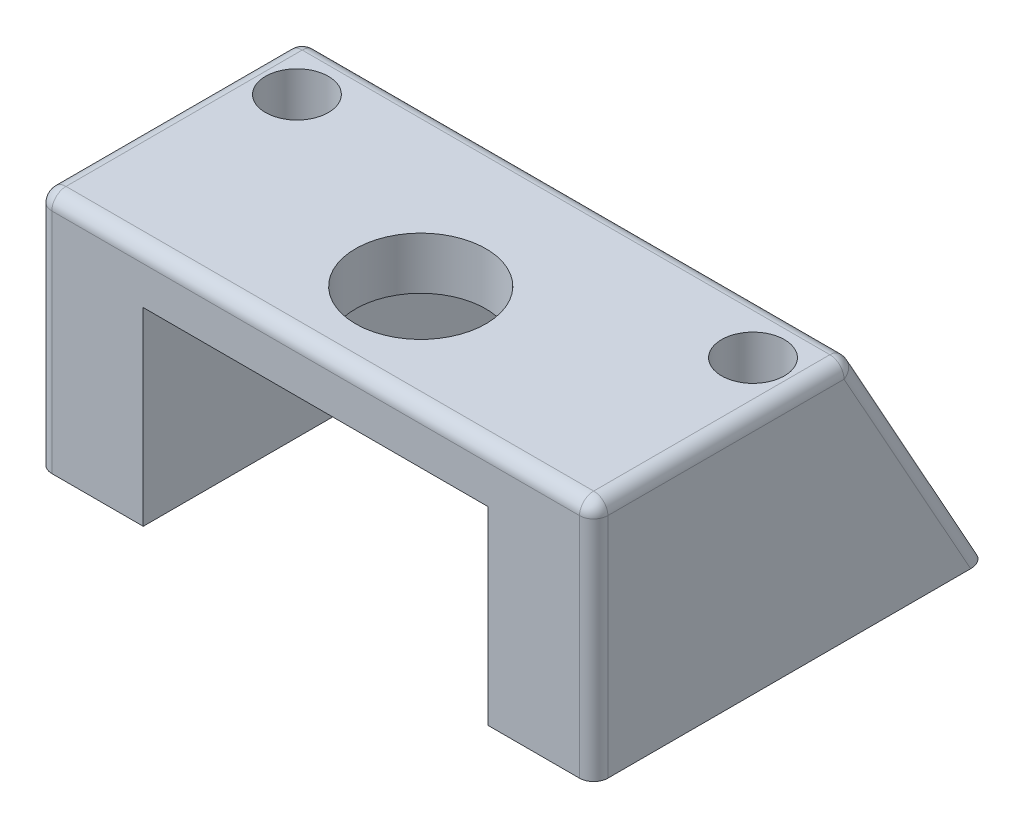
SolidWorks part; units mm, degrees
ref_plane "Front Plane" through (0, 0, 0) normal (0, 0, 1) x (1, 0, 0)
ref_plane "Top Plane" through (0, 0, 0) normal (0, 1, 0) x (1, 0, 0)
ref_plane "Right Plane" through (0, 0, 0) normal (1, 0, 0) x (0, 0, -1)
sketch "Sketch1" plane through (0, 0, 0) normal (1, 0, 0) x (0, 0, -1)
  line L0 (15.0876, -9.271) -> (4.7655, 9.271)
  line L1 (-15.0876, -9.271) -> (15.0876, -9.271)
  line L2 (-15.0876, -9.271) -> (-15.0876, 9.271)
  line L3 (-15.0876, 9.271) -> (15.0876, 9.271)
  line L4 (15.0876, -9.271) -> (15.0876, 9.271)
  line L5 (-15.0876, -9.271) -> (15.0876, 9.271) construction
  line L6 (-15.0876, 9.271) -> (15.0876, -9.271) construction
  line L7 (-15.0876, -9.271) -> (7.9487, 3.553) construction
  line L8 (-15.0876, 9.271) -> (-15.0876, 11.176) construction
  line L9 (-15.0876, 11.176) -> (4.7655, 11.176) construction
  line L10 (4.7655, 11.176) -> (4.7655, 9.271) construction
  line L12 (-14.0002, 13.081) -> (3.6782, 13.081) construction
  line L13 (-14.0002, 13.081) -> (-14.0002, 9.271) construction
  line L14 (-14.0002, 9.271) -> (3.6782, 9.271) construction
  line L15 (3.6782, 13.081) -> (3.6782, 9.271) construction
  line L16 (-14.0002, 13.081) -> (3.6782, 9.271) construction
  line L17 (-14.0002, 9.271) -> (3.6782, 13.081) construction
  arc A0 (-14.0002, 9.271) -> (-15.0876, 8.1836) centre (-14.0002, 8.1836) ccw
  arc A1 (3.6782, 9.271) -> (5.2944, 8.3209) centre (3.6782, 7.4212) cw
  point P0 (0, 0)
  point P10 (-5.161, 11.176)
  dimension "D1" = 18.542
  dimension "D2" = 30.1752
  dimension "D3" = 26.3652
  dimension "D4" = 1.905
  dimension "D5" = 17.6784
extrude "Boss-Extrude1" add sketch "Sketch1" along normal mid plane 42.672 contours L3 L2 L1 L0 | A0 L3 L2 | L3 A1 L0 region at (0, -0.6469, 2.3992) region at (0, 9.0714, -4.6482) region at (0, 9.0281, 14.8447)
sketch "Sketch2" plane through (0, 0, 0) normal (0, 0, 1) x (1, 0, 0)
  line L0 (21.336, -9.271) -> (-21.336, -9.271) construction
  line L1 (-13.2334, 5.271) -> (13.2334, 5.271)
  line L2 (-13.2334, 5.271) -> (-13.2334, -9.271)
  line L3 (-13.2334, -9.271) -> (13.2334, -9.271)
  line L4 (13.2334, 5.271) -> (13.2334, -9.271)
  line L5 (-13.2334, 5.271) -> (13.2334, -9.271) construction
  line L6 (-13.2334, -9.271) -> (13.2334, 5.271) construction
  line L8 (21.336, 9.271) -> (-21.336, 9.271) construction
  line L9 (21.336, -9.271) -> (21.336, 9.271) construction
  point P0 (0, -2)
  dimension "D1" = 8.1026
  dimension "D2" = 4
extrude "Cut-Extrude1" cut sketch "Sketch2" against normal through all both and the other way through all
sketch "Sketch3" plane through (0, 0, 0) normal (0, 1, 0) x (1, 0, 0)
  line L0 (21.336, -15.0876) -> (-21.336, -15.0876) construction
  line L8 (21.336, -15.0876) -> (21.336, 4.7655) construction
  line L9 (21.336, -1.4338) -> (21.336, -15.0876) construction
  circle A2 centre (0, -7.025) radius 2.5 construction
  circle A3 centre (0, -7.025) radius 5
  dimension "D1" = 5.5626
  dimension "D2" = 5
  dimension "D5" = 10
fillet "Fillet1" radius 1.0874 8 edges at (0, 9.271, -4.7655) (21.336, 9.271, 5.161) (0, 9.271, 15.0876) (-21.336, 9.271, 5.161) (-21.336, 0, -9.9266) (-21.336, 0, 15.0876) (21.336, 0, 15.0876) (21.336, 0, -9.9266)
extrude "Cut-Extrude2" cut sketch "Sketch3" against normal through all both and the other way through all
sketch "StepperAlignmentSketch" plane through (0, 0, 0) normal (0, 1, 0) x (1, 0, 0)
  line L0 (0, -7.025) -> (17.5, -15.025) construction
  line L1 (17.5, -15.025) -> (-17.5, -15.025) construction
  line L2 (-17.5, -15.025) -> (0, -7.025) construction
  line L3 (0, -7.025) -> (13.2334, -7.025) construction
  line L4 (13.2334, 6.9923) -> (13.2334, -15.0876) construction
  line L5 (17.5, 0.975) -> (-17.5, 0.975) construction
  line L6 (-17.5, 0.975) -> (0, -7.025) construction
  line L7 (0, -7.025) -> (17.5, 0.975) construction
  point P9 (0, -15.025)
  dimension "D1" = 19.2419
  dimension "D2" = 35
sketch "Sketch4" plane through (0, 0, 0) normal (0, 1, 0) x (1, 0, 0)
  line L0 (-21.336, -14.0002) -> (-13.2334, -14.0002)
  line L1 (-13.2334, 6.9923) -> (-13.2334, -15.0876) construction
  line L2 (-13.2334, -15.0876) -> (-20.2486, -15.0876) construction
  line L3 (-17.2847, -14.0002) -> (-17.2847, -15.0876) construction
  line L40 (-14.3208, -14.0002) -> (-14.3208, 14.0002)
  line L41 (-14.3208, 14.0002) -> (-20.2486, 14.0002)
  line L42 (-20.2486, 14.0002) -> (-20.2486, -14.0002)
  line L43 (-20.2486, 0) -> (-21.336, 0) construction
  line L44 (-17.9322, -1.4761) -> (-17.5, -1.5523) construction
  line L45 (-17.5, -1.2947) -> (-16.7237, -1.1578) construction
  line L46 (-16.7237, -1.1578) -> (-16.0411, -0.7637) construction
  line L47 (-17.2847, 14.0002) -> (-17.2847, 15.0876) construction
  line L48 (-13.2334, 15.0876) -> (-20.2486, 15.0876) construction
  line L49 (-16.0411, -0.7637) -> (-15.5344, -0.1598) construction
  line L50 (-14.3208, 0) -> (-13.2334, 0) construction
  line L51 (-21.336, -14.0002) -> (-21.336, 13.8431) construction
  line L52 (-15.5344, -0.1598) -> (-15.2648, 0.5809) construction
  line L53 (-15.2648, 0.5809) -> (-15.2648, 1.3691) construction
  line L54 (-15.2648, 1.3691) -> (-15.5344, 2.1098) construction
  line L55 (-15.5344, 2.1098) -> (-16.0411, 2.7137) construction
  line L56 (-21.336, -14.0002) -> (-21.336, 4.1263) construction
  line L57 (-21.336, -14.0002) -> (-21.336, 4.1263)
  line L58 (-16.0411, 2.7137) -> (-16.7237, 3.1078) construction
  line L59 (-16.7237, 3.1078) -> (-17.5, 3.2447) construction
  line L60 (-17.5, 3.2447) -> (-18.2763, 3.1078) construction
  line L61 (-18.2763, 3.1078) -> (-18.9589, 2.7137) construction
  line L62 (-18.9589, 2.7137) -> (-19.4656, 2.1098) construction
  line L63 (-19.4656, 2.1098) -> (-19.7352, 1.3691) construction
  line L64 (-19.7352, 1.3691) -> (-19.7352, 0.5809) construction
  line L65 (-19.7352, 0.5809) -> (-19.4656, -0.1598) construction
  line L66 (-19.4656, -0.1598) -> (-18.9589, -0.7637) construction
  line L67 (-18.9589, -0.7637) -> (-18.2763, -1.1578) construction
  line L68 (-18.2763, -1.1578) -> (-17.5, -1.2947) construction
  line L69 (-15.0111, 0.975) -> (-15.1612, 1.8263) construction
  line L70 (-15.1612, 1.8263) -> (-15.5934, 2.5748) construction
  line L71 (-15.5934, 2.5748) -> (-16.2555, 3.1305) construction
  line L72 (-16.2555, 3.1305) -> (-17.0678, 3.4261) construction
  line L73 (-17.0678, 3.4261) -> (-17.9322, 3.4261) construction
  line L74 (-17.9322, 3.4261) -> (-18.7445, 3.1305) construction
  line L75 (-18.7445, 3.1305) -> (-19.4066, 2.5748) construction
  line L76 (-19.4066, 2.5748) -> (-19.8388, 1.8263) construction
  line L77 (-19.8388, 1.8263) -> (-19.9889, 0.975) construction
  line L78 (-19.9889, 0.975) -> (-19.8388, 0.1237) construction
  line L79 (-19.8388, 0.1237) -> (-19.4066, -0.6248) construction
  line L80 (-19.4066, -0.6248) -> (-18.7445, -1.1805) construction
  line L81 (-18.7445, -1.1805) -> (-17.9322, -1.4761) construction
  line L82 (-17.9322, -1.4761) -> (-17.0678, -1.4761) construction
  line L83 (-17.0678, -1.4761) -> (-16.2555, -1.1805) construction
  line L84 (-16.2555, -1.1805) -> (-15.5934, -0.6248) construction
  line L85 (-15.5934, -0.6248) -> (-15.1612, 0.1237) construction
  line L86 (-15.1612, 0.1237) -> (-15.0111, 0.975) construction
  line L87 (-17.5, -1.5523) -> (-17.0678, -1.4761) construction
  line L89 (-17.5, -1.2947) -> (-16.5746, -1.2947) construction
  line L90 (-17.9322, -1.4761) -> (-17.7121, -1.3948) construction
  line L91 (-17.7121, -1.3948) -> (-17.5, -1.2947) construction
  line L92 (-17.5, -1.2947) -> (-17.2879, -1.3948) construction
  line L93 (-17.2879, -1.3948) -> (-17.0678, -1.4761) construction
  circle A1 centre (-17.5, 0.975) radius 2.2352 construction
  circle A2 centre (-17.5, 0.975) radius 2.4511 construction
  circle A75 centre (-17.5, 0.975) radius 3.9624
  arc A76 (-17.9322, -1.4761) -> (-17.7121, -1.3948) centre (-17.8918, -1.2469) ccw
  arc A77 (-17.7121, -1.3948) -> (-17.5, -1.2947) centre (-17.5, -1.5694) cw
  arc A78 (-17.5, -1.2947) -> (-17.2879, -1.3948) centre (-17.5, -1.5694) cw
  arc A79 (-17.2879, -1.3948) -> (-17.0678, -1.4761) centre (-17.1082, -1.2469) ccw
  arc A80 (-18.1112, -1.3245) -> (-17.9322, -1.4761) centre (-17.8918, -1.2469) ccw
  arc A81 (-18.2763, -1.1578) -> (-18.1112, -1.3245) centre (-18.3702, -1.416) cw
  arc A82 (-18.5099, -1.1794) -> (-18.2763, -1.1578) centre (-18.3702, -1.416) cw
  arc A83 (-18.7445, -1.1805) -> (-18.5099, -1.1794) centre (-18.6281, -0.9789) ccw
  circle A84 centre (-17.5, 0.975) radius 2.2352 construction
  arc A85 (-18.8608, -0.9768) -> (-18.7445, -1.1805) centre (-18.6281, -0.9789) ccw
  arc A86 (-18.9589, -0.7637) -> (-18.8608, -0.9768) centre (-19.1355, -0.9742) cw
  arc A87 (-19.1858, -0.704) -> (-18.9589, -0.7637) centre (-19.1355, -0.9742) cw
  arc A88 (-19.4066, -0.6248) -> (-19.1858, -0.704) centre (-19.2284, -0.4753) ccw
  circle A89 centre (-17.5, 0.975) radius 2.2352 construction
  arc A90 (-19.4463, -0.3936) -> (-19.4066, -0.6248) centre (-19.2284, -0.4753) ccw
  arc A91 (-19.4656, -0.1598) -> (-19.4463, -0.3936) centre (-19.7035, -0.2972) cw
  arc A92 (-19.6584, -0.0262) -> (-19.4656, -0.1598) centre (-19.7035, -0.2972) cw
  arc A93 (-19.8388, 0.1237) -> (-19.6584, -0.0262) centre (-19.6202, 0.2033) ccw
  circle A94 centre (-17.5, 0.975) radius 2.2352 construction
  arc A95 (-19.797, 0.3546) -> (-19.8388, 0.1237) centre (-19.6202, 0.2033) ccw
  arc A96 (-19.7352, 0.5809) -> (-19.797, 0.3546) centre (-20.0058, 0.5332) cw
  arc A97 (-19.8707, 0.7724) -> (-19.7352, 0.5809) centre (-20.0058, 0.5332) cw
  arc A98 (-19.9889, 0.975) -> (-19.8707, 0.7724) centre (-19.7562, 0.975) ccw
  circle A99 centre (-17.5, 0.975) radius 2.2352 construction
  arc A100 (-19.8707, 1.1776) -> (-19.9889, 0.975) centre (-19.7562, 0.975) ccw
  arc A101 (-19.7352, 1.3691) -> (-19.8707, 1.1776) centre (-20.0058, 1.4168) cw
  arc A102 (-19.797, 1.5954) -> (-19.7352, 1.3691) centre (-20.0058, 1.4168) cw
  arc A103 (-19.8388, 1.8263) -> (-19.797, 1.5954) centre (-19.6202, 1.7467) ccw
  circle A104 centre (-17.5, 0.975) radius 2.2352 construction
  arc A105 (-19.6584, 1.9762) -> (-19.8388, 1.8263) centre (-19.6202, 1.7467) ccw
  arc A106 (-19.4656, 2.1098) -> (-19.6584, 1.9762) centre (-19.7035, 2.2472) cw
  arc A107 (-19.4463, 2.3436) -> (-19.4656, 2.1098) centre (-19.7035, 2.2472) cw
  arc A108 (-19.4066, 2.5748) -> (-19.4463, 2.3436) centre (-19.2284, 2.4253) ccw
  circle A109 centre (-17.5, 0.975) radius 2.2352 construction
  arc A110 (-19.1858, 2.654) -> (-19.4066, 2.5748) centre (-19.2284, 2.4253) ccw
  arc A111 (-18.9589, 2.7137) -> (-19.1858, 2.654) centre (-19.1355, 2.9242) cw
  arc A112 (-18.8608, 2.9268) -> (-18.9589, 2.7137) centre (-19.1355, 2.9242) cw
  arc A113 (-18.7445, 3.1305) -> (-18.8608, 2.9268) centre (-18.6281, 2.9289) ccw
  circle A114 centre (-17.5, 0.975) radius 2.2352 construction
  arc A115 (-18.5099, 3.1294) -> (-18.7445, 3.1305) centre (-18.6281, 2.9289) ccw
  arc A116 (-18.2763, 3.1078) -> (-18.5099, 3.1294) centre (-18.3702, 3.366) cw
  arc A117 (-18.1112, 3.2745) -> (-18.2763, 3.1078) centre (-18.3702, 3.366) cw
  arc A118 (-17.9322, 3.4261) -> (-18.1112, 3.2745) centre (-17.8918, 3.1969) ccw
  circle A119 centre (-17.5, 0.975) radius 2.2352 construction
  arc A120 (-17.7121, 3.3448) -> (-17.9322, 3.4261) centre (-17.8918, 3.1969) ccw
  arc A121 (-17.5, 3.2447) -> (-17.7121, 3.3448) centre (-17.5, 3.5194) cw
  arc A122 (-17.2879, 3.3448) -> (-17.5, 3.2447) centre (-17.5, 3.5194) cw
  arc A123 (-17.0678, 3.4261) -> (-17.2879, 3.3448) centre (-17.1082, 3.1969) ccw
  circle A124 centre (-17.5, 0.975) radius 2.2352 construction
  arc A125 (-16.8888, 3.2745) -> (-17.0678, 3.4261) centre (-17.1082, 3.1969) ccw
  arc A126 (-16.7237, 3.1078) -> (-16.8888, 3.2745) centre (-16.6298, 3.366) cw
  arc A127 (-16.4901, 3.1294) -> (-16.7237, 3.1078) centre (-16.6298, 3.366) cw
  arc A128 (-16.2555, 3.1305) -> (-16.4901, 3.1294) centre (-16.3719, 2.9289) ccw
  circle A129 centre (-17.5, 0.975) radius 2.2352 construction
  arc A130 (-16.1392, 2.9268) -> (-16.2555, 3.1305) centre (-16.3719, 2.9289) ccw
  arc A131 (-16.0411, 2.7137) -> (-16.1392, 2.9268) centre (-15.8645, 2.9242) cw
  arc A132 (-15.8142, 2.654) -> (-16.0411, 2.7137) centre (-15.8645, 2.9242) cw
  arc A133 (-15.5934, 2.5748) -> (-15.8142, 2.654) centre (-15.7716, 2.4253) ccw
  circle A134 centre (-17.5, 0.975) radius 2.2352 construction
  arc A135 (-15.5537, 2.3436) -> (-15.5934, 2.5748) centre (-15.7716, 2.4253) ccw
  arc A136 (-15.5344, 2.1098) -> (-15.5537, 2.3436) centre (-15.2965, 2.2472) cw
  arc A137 (-15.3416, 1.9762) -> (-15.5344, 2.1098) centre (-15.2965, 2.2472) cw
  arc A138 (-15.1612, 1.8263) -> (-15.3416, 1.9762) centre (-15.3798, 1.7467) ccw
  circle A139 centre (-17.5, 0.975) radius 2.2352 construction
  arc A140 (-15.203, 1.5954) -> (-15.1612, 1.8263) centre (-15.3798, 1.7467) ccw
  arc A141 (-15.2648, 1.3691) -> (-15.203, 1.5954) centre (-14.9942, 1.4168) cw
  arc A142 (-15.1293, 1.1776) -> (-15.2648, 1.3691) centre (-14.9942, 1.4168) cw
  arc A143 (-15.0111, 0.975) -> (-15.1293, 1.1776) centre (-15.2438, 0.975) ccw
  circle A144 centre (-17.5, 0.975) radius 2.2352 construction
  arc A145 (-15.1293, 0.7724) -> (-15.0111, 0.975) centre (-15.2438, 0.975) ccw
  arc A146 (-15.2648, 0.5809) -> (-15.1293, 0.7724) centre (-14.9942, 0.5332) cw
  arc A147 (-15.203, 0.3546) -> (-15.2648, 0.5809) centre (-14.9942, 0.5332) cw
  arc A148 (-15.1612, 0.1237) -> (-15.203, 0.3546) centre (-15.3798, 0.2033) ccw
  circle A149 centre (-17.5, 0.975) radius 2.2352 construction
  arc A150 (-15.3416, -0.0262) -> (-15.1612, 0.1237) centre (-15.3798, 0.2033) ccw
  arc A151 (-15.5344, -0.1598) -> (-15.3416, -0.0262) centre (-15.2965, -0.2972) cw
  arc A152 (-15.5537, -0.3936) -> (-15.5344, -0.1598) centre (-15.2965, -0.2972) cw
  arc A153 (-15.5934, -0.6248) -> (-15.5537, -0.3936) centre (-15.7716, -0.4753) ccw
  circle A154 centre (-17.5, 0.975) radius 2.2352 construction
  arc A155 (-15.8142, -0.704) -> (-15.5934, -0.6248) centre (-15.7716, -0.4753) ccw
  arc A156 (-16.0411, -0.7637) -> (-15.8142, -0.704) centre (-15.8645, -0.9742) cw
  arc A157 (-16.1392, -0.9768) -> (-16.0411, -0.7637) centre (-15.8645, -0.9742) cw
  arc A158 (-16.2555, -1.1805) -> (-16.1392, -0.9768) centre (-16.3719, -0.9789) ccw
  circle A159 centre (-17.5, 0.975) radius 2.2352 construction
  arc A160 (-16.4901, -1.1794) -> (-16.2555, -1.1805) centre (-16.3719, -0.9789) ccw
  arc A161 (-16.7237, -1.1578) -> (-16.4901, -1.1794) centre (-16.6298, -1.416) cw
  arc A162 (-16.8888, -1.3245) -> (-16.7237, -1.1578) centre (-16.6298, -1.416) cw
  arc A163 (-17.0678, -1.4761) -> (-16.8888, -1.3245) centre (-17.1082, -1.2469) ccw
  circle A164 centre (-17.5, 0.975) radius 2.2352 construction
  point P246 (-17.5, 0.975)
  dimension "D1" = 4.4704
  dimension "D2" = 4.9022
  dimension "D3" = 7.9248
  dimension "D4" = 18
  dimension "D5" = 0.2748
  dimension "D6" = 0.2327
extrude "Cut-Extrude3" cut sketch "Sketch4" along normal blind 16.9672 from surface contours L42 L0 L40 | A79 A163 A162 A161 A160 A158 A157 A156 A155 A153 A152 A151 A150 A148 A147 A146 A145 A143 A142 A141 A140 A138 A137 A136 A135 A133 A132 A131 A130 A128 A127 A126 A125 A123 A122 A121 A120 A118 A117 A116 A115 A113 A112 A111 A110 A108 A107 A106 A105 A103 A102 | L40 A75 L42 A163 A79 A78 A77 A76 A80 A81 A82 A83 A85 A86 A87 A88 A90 A91 A92 A93 A95 A96 A97 A98 A100 A101 A102 A103 A105 A106 A107 A108 A110 A111 A112 A113 A115 A116 A117 A118 A120 A121 A122 A123 A125 A126 A127 A128 A130 region at (-17.2672, 0, 8.2776) region at (-20.1497, 0, -0.975) region at (-17.5, 0, -0.975) starting at face at (-18.3477, -9.271, 0.0208)
ref_plane "Plane2" through (-17.2847, 0, 0) normal (-1, 0, 0) x (0, 0, 1)
sketch "Sketch7" plane through (-17.2847, 0, 0) normal (-1, 0, 0) x (0, 0, 1)
  line L8 (-4.9374, -9.271) -> (-3.34, -9.271) construction
  line L9 (-4.9374, -9.271) -> (-3.34, -9.271) construction
  line L10 (-3.34, 7.6962) -> (-3.34, -9.271) construction
  line L11 (-3.34, 7.6962) -> (-3.34, -9.271) construction
  line L12 (-3.34, -9.271) -> (-3.34, 7.6962)
  line L16 (-3.34, 7.6962) -> (-4.3977, 7.6962)
  line L17 (-4.1263, 8.1836) -> (-13.8431, -9.271) construction
  line L18 (-4.3977, 7.6962) -> (-13.8431, -9.271)
  line L19 (14.0002, -9.271) -> (-13.8431, -9.271) construction
  line L20 (-3.34, -9.271) -> (-13.8431, -9.271)
extrude "Cut-Extrude4" cut sketch "Sketch7" against normal up to surface and the other way up to surface contours L20 L12 L16 L18 region at (-17.2847, -3.0978, -6.8733) up to face at (-14.3208, -0.7874, 5.3301) other way up to face at (-20.2486, -0.7874, 5.0856)
extrude "Boss-Extrude2" add sketch "Sketch4<3>" along normal up to surface (7.6962 mm away) and the other way up to surface (9.271 mm away) contours L40 A75 L42 A163 A79 A78 A77 A76 A80 A81 A82 A83 A85 A86 A87 A88 A90 A91 A92 A93 A95 A96 A97 A98 A100 A101 A102 A103 A105 A106 A107 A108 A110 A111 A112 A113 A115 A116 A117 A118 A120 A121 A122 A123 A125 A126 A127 A128 A130 | A79 A163 A162 A161 A160 A158 A157 A156 A155 A153 A152 A151 A150 A148 A147 A146 A145 A143 A142 A141 A140 A138 A137 A136 A135 A133 A132 A131 A130 A128 A127 A126 A125 A123 A122 A121 A120 A118 A117 A116 A115 A113 A112 A111 A110 A108 A107 A106 A105 A103 A102 region at (-20.1497, 0, -0.975) region at (-17.5, 0, -0.975) up to face at (-17.3565, 7.6962, 1.645) other way up to face at (-18.3477, -9.271, 0.0208)
sketch "Sketch4<3>" plane through (0, 0, 0) normal (0, 1, 0) x (1, 0, 0) same geometry as "Sketch4"
sketch "Sketch8" plane through (-17.2847, 0, 0) normal (-1, 0, 0) x (0, 0, 1)
  line L1 (-4.3977, 7.6962) -> (-3.829, 7.6962) construction
  line L2 (-13.8431, -9.271) -> (-4.3977, 7.6962) construction
  line L4 (-4.3977, 7.6962) -> (-3.829, 7.6962)
  line L5 (-13.8431, -9.271) -> (-4.3977, 7.6962)
  line L6 (-13.8431, -9.271) -> (-3.829, -9.271) construction
  line L7 (-13.8431, -9.271) -> (-3.829, -9.271)
  line L8 (-3.34, 7.6962) -> (-13.8431, -9.271)
  line L9 (-3.34, 7.6962) -> (-4.3977, 7.6962) construction
  line L10 (-3.34, 7.6962) -> (-4.3977, 7.6962)
  line L11 (-3.34, -9.271) -> (-13.8431, -9.271) construction
  line L12 (-3.34, -9.271) -> (-13.8431, -9.271)
  line L13 (-3.34, -9.271) -> (-3.34, 7.6962)
extrude "Boss-Extrude3" add sketch "Sketch8" against normal up to surface and the other way up to surface contours L4 L5 region at (-17.2847, 2.0405, -7.1936) up to face at (-14.3208, -0.7874, 7.6951) other way up to face at (-20.2486, -0.7874, 7.9396)
extrude "Cut-Extrude5" cut sketch "Sketch4<4>" along normal blind 8.001 from surface contours A79 A163 A162 A161 A160 A158 A157 A156 A155 A153 A152 A151 A150 A148 A147 A146 A145 A143 A142 A141 A140 A138 A137 A136 A135 A133 A132 A131 A130 A128 A127 A126 A125 A123 A122 A121 A120 A118 A117 A116 A115 A113 A112 A111 A110 A108 A107 A106 A105 A103 A102 region at (-17.5, 0, -0.975) starting at face at (18.3477, -9.271, 0.0208)
sketch "Sketch4<4>" plane through (0, 0, 0) normal (0, 1, 0) x (1, 0, 0) same geometry as "Sketch4"
ref_plane "Plane3" through (17.2847, 0, 0) normal (-1, 0, 0) x (0, 0, 1)
sketch "Sketch9" plane through (17.2847, 0, 0) normal (-1, 0, 0) x (0, 0, 1)
  line L0 (-13.8431, -9.271) -> (-3.34, 7.6962) construction
  line L1 (14.0002, 7.6962) -> (14.0002, -9.271) construction
  line L2 (14.0002, 7.6962) -> (1.39, 7.6962) construction
  line L3 (-13.8431, -9.271) -> (-3.34, 7.6962)
  line L4 (14.0002, 7.6962) -> (14.0002, -9.271)
  line L5 (14.0002, 7.6962) -> (1.39, 7.6962)
  line L6 (1.39, 7.6962) -> (-3.34, 7.6962)
  line L7 (14.0002, -9.271) -> (-13.8431, -9.271) construction
  line L8 (14.0002, -9.271) -> (-13.8431, -9.271)
extrude "Cut-Extrude6" cut sketch "Sketch9" against normal mid plane 5.9279
mirror "Mirror7" about plane through (0, 0, 0) normal (1, 0, 0) of "Boss-Extrude2"
mirror "Mirror8" about plane through (0, 0, 0) normal (1, 0, 0) of "Cut-Extrude5"
sketch "Sketch12" plane through (0, 0, 0) normal (1, 0, 0) x (0, 0, -1)
  line L0 (13.8431, -9.271) -> (4.6307, 7.2776)
  line L1 (-14.0002, -9.271) -> (13.8431, -9.271) construction
  line L2 (4.6307, 7.2776) -> (-14.0002, 7.2776)
  line L3 (-14.0002, 7.2776) -> (-14.0002, -9.271)
  line L4 (6.9923, 5.271) -> (-15.0876, 5.271) construction
  line L5 (6.9923, 5.271) -> (-15.0876, 5.271) construction
  line L6 (5.0764, 8.7125) -> (15.0876, -9.271) construction
  line L7 (13.8431, -9.271) -> (3.829, -9.271) construction
  line L8 (-1.879, -9.271) -> (-14.0002, -9.271) construction
  line L9 (13.8431, -9.271) -> (3.829, -9.271) construction
  line L10 (-1.879, -9.271) -> (-14.0002, -9.271) construction
  line L11 (-14.0002, -9.271) -> (13.8431, -9.271)
  dimension "D1" = 2.0066
extrude "Cut-Extrude7" cut sketch "Sketch12" against normal up to surface and the other way up to surface up to face at (-13.2334, -2, 2.0238) other way up to face at (13.2334, -2, 2.0238)
sketch "Sketch11" plane through (0, 0, 0) normal (0, 1, 0) x (1, 0, 0)
  line L4 (-13.2334, 4.6307) -> (-13.2334, -14.0002) construction
  line L5 (-13.2334, -14.0002) -> (13.2334, -14.0002) construction
  line L6 (13.2334, 4.6307) -> (13.2334, -14.0002) construction
  line L7 (-13.2334, 4.6307) -> (13.2334, 4.6307) construction
  line L9 (-13.2334, 4.6307) -> (-13.2334, -14.0002)
  line L10 (-13.2334, -14.0002) -> (13.2334, -14.0002)
  line L11 (13.2334, 4.6307) -> (13.2334, -14.0002)
  line L12 (-13.2334, 4.6307) -> (13.2334, 4.6307)
  line L13 (13.2334, 5.7478) -> (-13.2334, 5.7478) construction
  line L14 (-0.8128, -5.7478) -> (0.8128, -5.7478)
  line L15 (-0.8128, -5.7478) -> (-0.8128, 5.7478)
  line L16 (-0.8128, 5.7478) -> (0.8128, 5.7478)
  line L17 (0.8128, -5.7478) -> (0.8128, 5.7478)
  line L18 (-0.8128, -5.7478) -> (0.8128, 5.7478) construction
  line L19 (-0.8128, 5.7478) -> (0.8128, -5.7478) construction
  circle A2 centre (0, -7.025) radius 5 construction
  circle A3 centre (0, -7.025) radius 5
  circle A4 centre (0, -7.025) radius 7.2864
  point P8 (0, 0)
  dimension "D1" = 1.6256
  dimension "D2" = 5.4864
extrude "Boss-Extrude5" add sketch "Sketch11" along normal up to surface (7.2776 mm away) from surface contours A4 L17 L12 L15 | L10 A4 L17 A3 L15 | L17 A4 L15 A3 | L12 L17 L16 L15 region at (0, 0, -5.1892) region at (0, 0, -2.4385) region at (-7.0536, 0, 6.3831) region at (0, 0, 0.9005) up to face at (0, 7.2776, 4.6848) starting at face at (0, 5.271, -6.37)
sketch "Sketch14" plane through (0, 9.271, 0) normal (0, 1, 0) x (1, 0, 0)
  line L0 (0, 0) -> (0, 4.1263) construction
  line L1 (20.2486, 4.1263) -> (-20.2486, 4.1263) construction
  circle A0 centre (-17.5, 0.975) radius 3.9624 construction
  circle A1 centre (-17.5, 0.975) radius 3.9624 construction
  circle A2 centre (-17.5, 0.975) radius 2.413
  circle A5 centre (17.5, 0.975) radius 2.413
  dimension "D1" = 4.826
extrude "Cut-Extrude8" cut sketch "Sketch14" against normal blind 9.3472
sketch "Sketch15" plane through (0, -0.0762, 0) normal (0, 1, 0) x (1, 0, 0)
  circle A0 centre (-17.5, 0.975) radius 1.143
  circle A1 centre (17.5, 0.975) radius 1.143
  dimension "D1" = 2.286
extrude "Cut-Extrude9" cut sketch "Sketch15" against normal up to next
